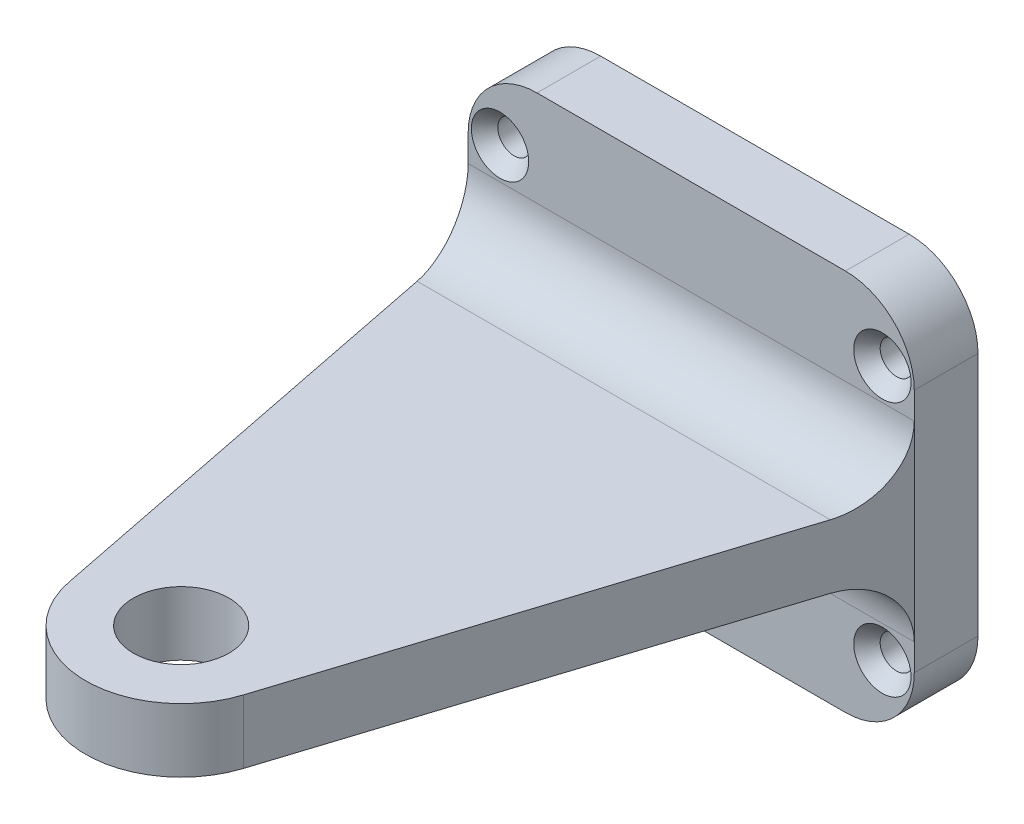
SolidWorks part; units mm, degrees
material "6061-T6 (SS)"
ref_plane "XY" through (0, 0, 0) normal (0, 0, 1) x (1, 0, 0)
ref_plane "XZ" through (0, 0, 0) normal (0, 1, 0) x (1, 0, 0)
ref_plane "YZ" through (0, 0, 0) normal (1, 0, 0) x (0, 0, -1)
ref_axis "X" through (-24.4475, 0, 0) along (1, 0, 0)
ref_axis "Y" through (0, -20.955, 0) along (0, 1, 0)
ref_axis "Z" through (0, 0, 87.8777) along (0, 0, -1)
sketch "Sketch1" plane through (0, 0, 0) normal (0, 0, 1) x (1, 0, 0)
  line L1 (-22.225, -19.05) -> (22.225, -19.05)
  line L2 (-22.225, -19.05) -> (-22.225, 19.05)
  line L3 (-22.225, 19.05) -> (22.225, 19.05)
  line L4 (22.225, -19.05) -> (22.225, 19.05)
  line L5 (-22.225, -19.05) -> (22.225, 19.05) construction
  line L6 (-22.225, 19.05) -> (22.225, -19.05) construction
  point P0 (0, 0)
  dimension "D1" = 38.1
  dimension "D2" = 44.45
extrude "Boss-Extrude1" add sketch "Sketch1" along normal blind 6.35
hole_wizard "CSK for #4 Flat Head Machine Screw1" positions "Sketch2" profile "Sketch3" countersink size "#4" standard "ANSI Inch" end condition up to next
sketch "Sketch2" plane through (0, 0, 6.35) normal (0, 0, 1) x (1, 0, 0)
  line L1 (-19.05, 12.7) -> (19.05, 12.7)
  line L2 (-19.05, 12.7) -> (-19.05, -12.7)
  line L3 (-19.05, -12.7) -> (19.05, -12.7)
  line L4 (19.05, 12.7) -> (19.05, -12.7)
  line L5 (0, -12.7) -> (0, 12.7) construction
  point P0 (-19.05, 12.7)
  point P5 (19.05, -12.7)
  point P108 (-19.05, -12.7)
  point P109 (19.05, 12.7)
  dimension "D1" = 25.4
  dimension "D2" = 38.1
sketch "Sketch3" plane through (-19.05, 12.7, 6.35) normal (1, 0, 0) x (0, -1, 0)
  line L0 (0, 0) -> (0, 6.35)
  line L1 (0, 6.35) -> (1.6319, 6.35)
  line L2 (1.6319, 6.35) -> (1.6319, 1.4098)
  line L3 (1.6319, 1.4098) -> (2.8575, 0)
  line L5 (2.8575, 0) -> (0, 0)
  line L6 (-1.6319, 1.4098) -> (-2.8575, 0) construction
  line L11 (0, -6.35) -> (0, 107.95) construction
  dimension "Thru Hole Dia." = 3.2639
  dimension "Thru Hole Depth" = 6.35
  dimension "Near C'Sink Dia." = 5.715
  dimension "Near C'Sink Angle" = 82
sketch "Sketch4" plane through (0, 0, 0) normal (0, 1, 0) x (1, 0, 0)
  line L0 (0, 0) -> (-3, -54.168) construction
  line L1 (-12.3419, -56.0266) -> (-22.225, -6.35)
  line L2 (-22.225, -6.35) -> (22.225, -6.35) construction
  line L3 (6.0759, -57.0584) -> (22.225, -6.35)
  line L4 (-22.225, -6.35) -> (22.225, -6.35)
  line L5 (22.225, 0) -> (-22.225, 0) construction
  circle A0 centre (-3, -54.168) radius 8.382 construction
  circle A1 centre (-3, -54.168) radius 4.7625
  arc A2 (-12.3419, -56.0266) -> (6.0759, -57.0584) centre (-3, -54.168) ccw
  dimension "D1" = 16.764
  dimension "D3" = 9.525
  dimension "D4" = 19.05
  dimension "D2" = 54.168
  dimension "D5" = 3
extrude "Boss-Extrude2" add sketch "Sketch4" along normal mid plane 6.35
fillet "Fillet2" radius 6.858 4 edges at (-22.225, 19.05, 3.175) (-22.225, -19.05, 3.175) (22.225, -19.05, 3.175) (22.225, 19.05, 3.175)
fillet "Fillet3" radius 6.35 2 edges at (0, 3.175, 6.35) (0, -3.175, 6.35)
